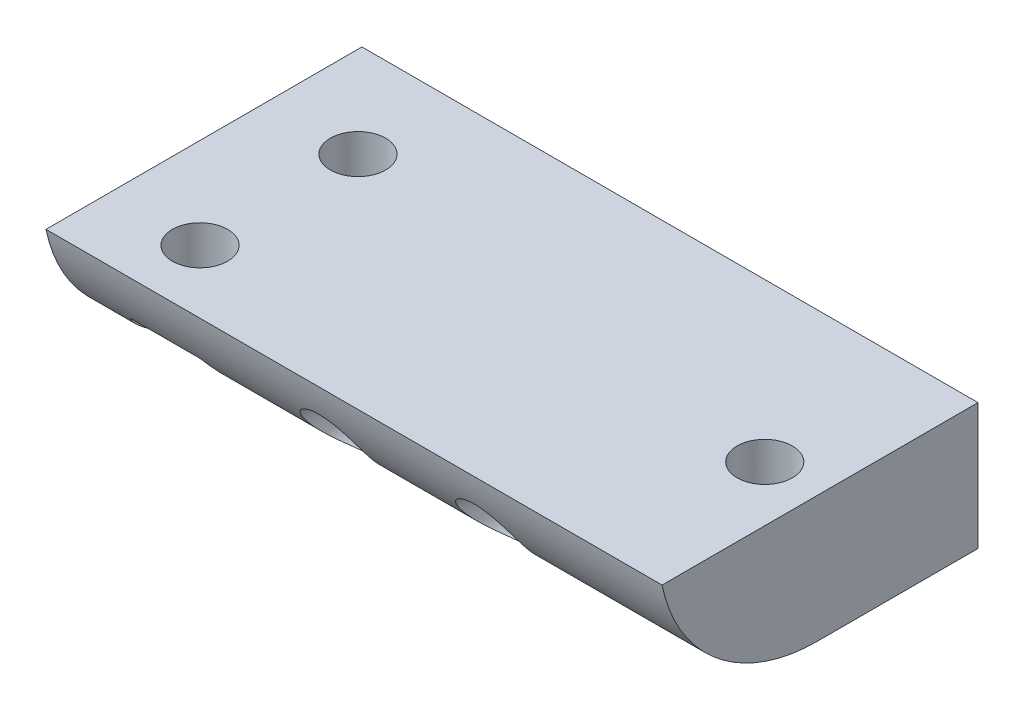
SolidWorks part; units mm, degrees
ref_plane "Front Plane" through (0, 0, 0) normal (0, 0, 1) x (1, 0, 0)
ref_plane "Top Plane" through (0, 0, 0) normal (0, 1, 0) x (1, 0, 0)
ref_plane "Right Plane" through (0, 0, 0) normal (1, 0, 0) x (0, 0, -1)
sketch "Sketch1" plane through (0, 0, 0) normal (0, 0, 1) x (1, 0, 0)
  line L1 (-6.6353, 11.7979) -> (32.3647, 11.7979)
  line L2 (-6.6353, 11.7979) -> (-6.6353, 3.7979)
  line L3 (-6.6353, 3.7979) -> (32.3647, 3.7979)
  line L4 (32.3647, 11.7979) -> (32.3647, 3.7979)
  circle A0 centre (9.8897, 7.5479) radius 2
  circle A1 centre (19.7397, 7.5479) radius 2
  dimension "D1" = 4
  dimension "D3" = 9.85
  dimension "D2" = 39
  dimension "D4" = 8
  dimension "D5" = 4.25
  dimension "D6" = 12.625
extrude "Boss-Extrude1" add sketch "Sketch1" along normal blind 20
sketch "Sketch2" plane through (0, 11.7979, 0) normal (0, 1, 0) x (1, 0, 0)
  line L0 (32.3647, -20) -> (-6.6353, -20) construction
  line L1 (-6.6353, -20) -> (-6.6353, 0) construction
  line L2 (32.3647, -20) -> (32.3647, 0) construction
  circle A0 centre (28.8647, -10) radius 1.75
  circle A1 centre (-0.8853, -14) radius 1.75
  circle A2 centre (-0.8853, -4) radius 1.75
  dimension "D2" = 3.5
  dimension "D3" = 6
  dimension "D1" = 10
  dimension "D4" = 10
  dimension "D5" = 5.75
  dimension "D6" = 3.5
extrude "Cut-Extrude3" cut sketch "Sketch2" against normal up to next
fillet "Fillet1" radius 10 1 edges at (12.8647, 3.7979, 0)
sketch "Sketch3" plane through (0, 3.7979, 0) normal (0, -1, 0) x (1, 0, 0)
  circle A0 centre (-0.8853, 14) radius 3.1
  circle A1 centre (28.8647, 10) radius 3.1
  circle A2 centre (-0.8853, 4) radius 3.1
  dimension "D1" = 6.2
extrude "Cut-Extrude4" cut sketch "Sketch3" against normal blind 4
ref_plane "Plane1" through (0, 0, 30) normal (0, 0, 1) x (1, 0, 0)
mirror "Mirror1" about plane through (0, 0, 30) normal (0, 0, 1) of bodies 103
sketch "Sketch4" plane through (0, 11.7979, 0) normal (0, 1, 0) x (1, 0, 0)
  line L1 (-10.5916, 5.3042) -> (38.9242, 5.3042)
  line L2 (-10.5916, 5.3042) -> (-10.5916, -23.4772)
  line L3 (-10.5916, -23.4772) -> (38.9242, -23.4772)
  line L4 (38.9242, 5.3042) -> (38.9242, -23.4772)
extrude "Cut-Extrude6" cut sketch "Sketch4" against normal through all both and the other way through all
